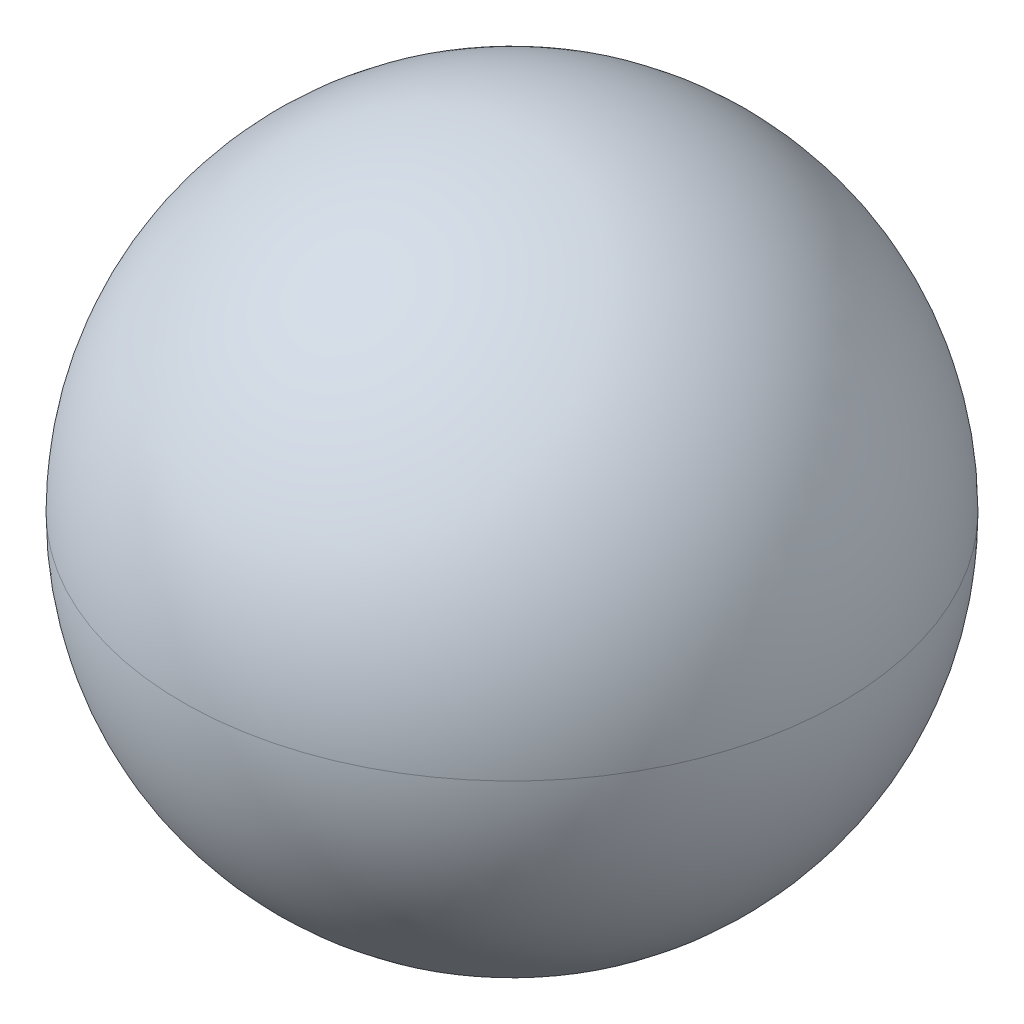
SolidWorks part; units mm, degrees
ref_plane "前视基准面" through (0, 0, 0) normal (0, 0, 1) x (1, 0, 0)
ref_plane "上视基准面" through (0, 0, 0) normal (0, 1, 0) x (1, 0, 0)
ref_plane "右视基准面" through (0, 0, 0) normal (1, 0, 0) x (0, 0, -1)
sketch "草图1" plane through (0, 0, 0) normal (0, 0, 1) x (1, 0, 0)
  line L0 (0, 124.4874) -> (0, -127.4975) construction
  line L1 (0, 108) -> (0, -108)
  arc A0 (0, -108) -> (0, 108) centre (0, 0) ccw
  dimension "D1" = 216
revolve "旋转1" add sketch "草图1" angle 360 about L0
ref_plane "基准面1" through (0, 0, 34) normal (0, 0, 1) x (1, 0, 0)
ref_axis "基准轴1" through (0, -124.9668, 0) along (0, 1, 0)
ref_point "点1"
other "使用曲面切除1" [suppressed]
split line "分割线1"
